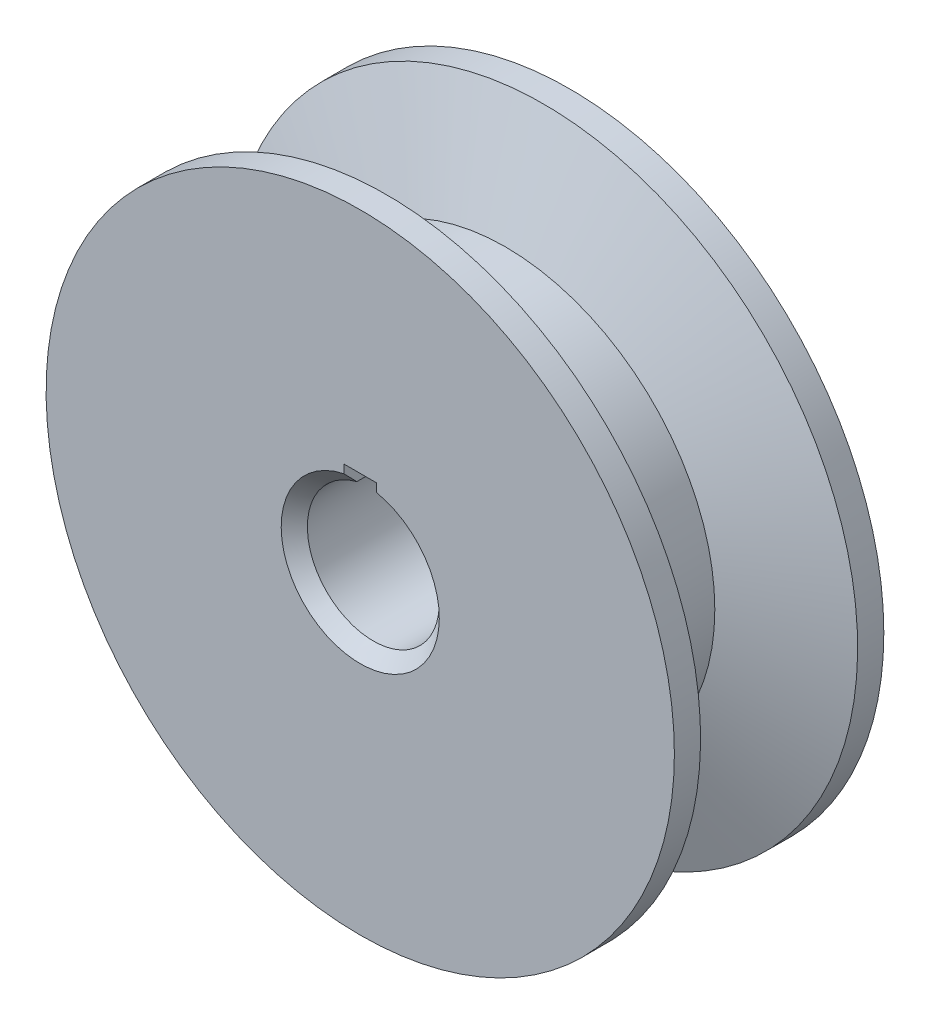
SolidWorks part; units mm, degrees
material "6061-T6 (SS)"
ref_plane "Front Plane" through (0, 0, 0) normal (0, 0, 1) x (1, 0, 0)
ref_plane "Top Plane" through (0, 0, 0) normal (0, 1, 0) x (1, 0, 0)
ref_plane "Right Plane" through (0, 0, 0) normal (1, 0, 0) x (0, 0, -1)
sketch "Sketch1" plane through (0, 0, 0) normal (0, 0, 1) x (1, 0, 0)
  circle A0 centre (0, 0) radius 19.05
  circle A1 centre (0, 0) radius 4
  dimension "D1" = 38.1
  dimension "D2" = 8
extrude "Extrude1" add sketch "Sketch1" along normal mid plane 12.7
sketch "Sketch2" plane through (0, 0, 0) normal (1, 0, 0) x (0, 0, -1)
  line L0 (-4.7625, 19.05) -> (4.7625, 19.05)
  line L2 (4.7625, 19.05) -> (2.4513, 12.7)
  line L3 (2.4513, 12.7) -> (-2.4513, 12.7)
  line L4 (-2.4513, 12.7) -> (-4.7625, 19.05)
  line L5 (-6.35, 0) -> (6.35, 0) construction
  line L6 (-6.35, 19.05) -> (-6.35, -19.05) construction
  line L7 (6.35, -19.05) -> (6.35, 19.05) construction
  point P2 (0, 19.05)
  point P5 (0, 12.7)
  dimension "D1" = 19.05
  dimension "D2" = 6.35
  dimension "D3" = 9.525
  dimension "D4" = 40
chamfer "Chamfer1" distance 0.7937 angle 45 2 edges at (4, 0, -6.35) (4, 0, 6.35)
revolve "Cut-Revolve1" cut sketch "Sketch2" angle 360 about L5
sketch "Sketch3" plane through (0, 0, 6.35) normal (0, 0, 1) x (1, 0, 0)
  line L0 (0, 0) -> (0, 4) construction
  line L2 (-1, 5.2) -> (1, 5.2)
  line L3 (-1, 5.2) -> (-1, 2.8)
  line L4 (-1, 2.8) -> (1, 2.8)
  line L5 (1, 5.2) -> (1, 2.8)
  line L6 (-1, 5.2) -> (1, 2.8) construction
  line L7 (-1, 2.8) -> (1, 5.2) construction
  circle A0 centre (0, 0) radius 4 construction
  dimension "D1" = 2.8
  dimension "D2" = 2
extrude "Cut-Extrude1" cut sketch "Sketch3" against normal through all contours L4 L5 L2 L3
